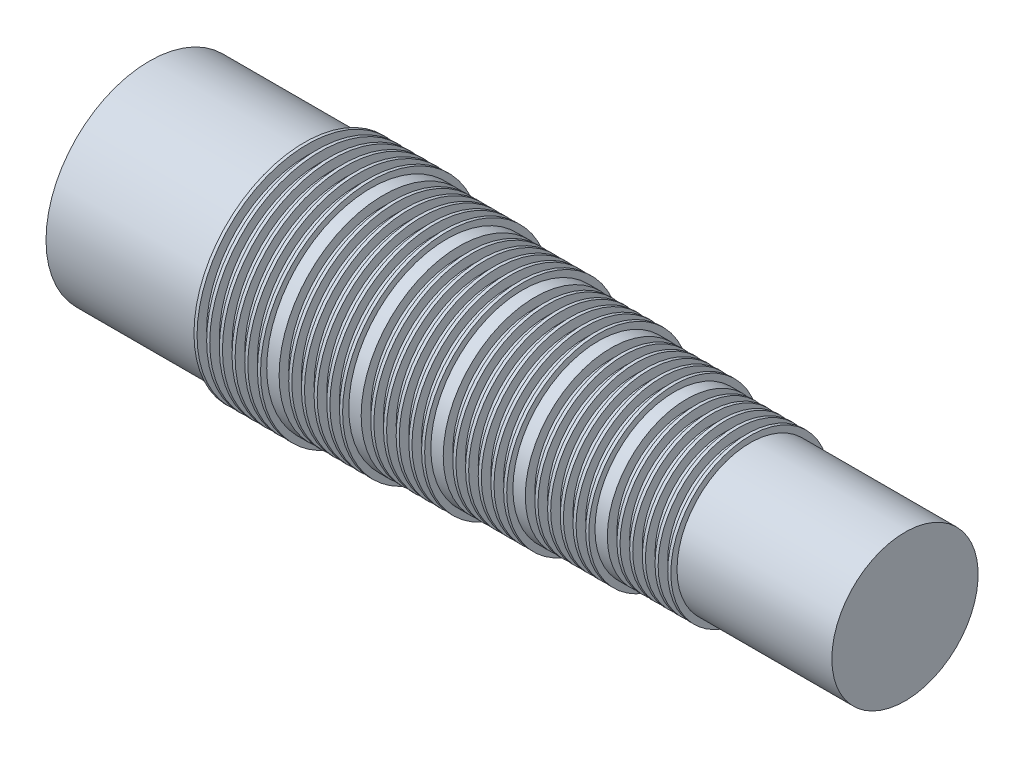
SolidWorks part; units mm, degrees
ref_plane "Front Plane" through (0, 0, 0) normal (0, 0, 1) x (1, 0, 0)
ref_plane "Top Plane" through (0, 0, 0) normal (0, 1, 0) x (1, 0, 0)
ref_plane "Right Plane" through (0, 0, 0) normal (1, 0, 0) x (0, 0, -1)
sketch "Sketch1" plane through (0, 0, 0) normal (0, 0, 1) x (1, 0, 0)
  line L24 (12.954, 9.048) -> (12.954, 8.2606)
  line L25 (12.954, 8.2606) -> (13.7414, 8.2606)
  line L26 (13.7414, 8.2606) -> (13.7414, 9.048)
  line L27 (13.7414, 9.048) -> (13.9954, 9.048)
  line L28 (13.9954, 9.048) -> (13.9954, 8.2606)
  line L29 (13.9954, 8.2606) -> (14.7828, 8.2606)
  line L30 (14.7828, 8.2606) -> (14.7828, 9.048)
  line L31 (14.7828, 9.048) -> (15.0368, 9.048)
  line L32 (15.0368, 9.048) -> (15.0368, 8.2606)
  line L33 (15.0368, 8.2606) -> (15.8242, 8.2606)
  line L34 (15.8242, 8.2606) -> (15.8242, 9.048)
  line L35 (15.8242, 9.048) -> (16.0782, 9.048)
  line L36 (16.0782, 9.048) -> (16.0782, 8.2606)
  line L37 (16.0782, 8.2606) -> (16.8656, 8.2606)
  line L38 (16.8656, 8.2606) -> (16.8656, 9.048)
  line L39 (16.8656, 9.048) -> (17.1196, 9.048)
  line L40 (17.1196, 9.048) -> (17.1196, 8.2606)
  line L41 (17.1196, 8.2606) -> (17.907, 8.2606)
  line L42 (17.907, 8.2606) -> (17.907, 9.048)
  line L43 (17.907, 9.048) -> (18.161, 9.048)
  line L44 (18.161, 9.048) -> (18.161, 8.54)
  line L45 (18.161, 8.54) -> (19.177, 8.54)
  line L46 (19.177, 8.54) -> (19.177, 7.7526)
  line L47 (19.177, 7.7526) -> (19.9644, 7.7526)
  line L48 (19.9644, 7.7526) -> (19.9644, 8.54)
  line L49 (19.9644, 8.54) -> (20.2184, 8.54)
  line L50 (20.2184, 8.54) -> (20.2184, 7.7526)
  line L51 (20.2184, 7.7526) -> (21.0058, 7.7526)
  line L52 (21.0058, 7.7526) -> (21.0058, 8.54)
  line L53 (21.0058, 8.54) -> (21.2598, 8.54)
  line L54 (21.2598, 8.54) -> (21.2598, 7.7526)
  line L55 (21.2598, 7.7526) -> (22.0472, 7.7526)
  line L56 (22.0472, 7.7526) -> (22.0472, 8.54)
  line L57 (22.0472, 8.54) -> (22.3012, 8.54)
  line L58 (22.3012, 8.54) -> (22.3012, 7.7526)
  line L59 (22.3012, 7.7526) -> (23.0886, 7.7526)
  line L60 (23.0886, 7.7526) -> (23.0886, 8.54)
  line L61 (23.0886, 8.54) -> (23.3426, 8.54)
  line L62 (23.3426, 8.54) -> (23.3426, 7.7526)
  line L63 (23.3426, 7.7526) -> (24.13, 7.7526)
  line L64 (24.13, 7.7526) -> (24.13, 8.54)
  line L65 (24.13, 8.54) -> (24.384, 8.54)
  line L66 (24.384, 8.54) -> (24.384, 8.032)
  line L67 (24.384, 8.032) -> (25.4, 8.032)
  line L68 (25.4, 8.032) -> (25.4, 7.2446)
  line L69 (25.4, 7.2446) -> (26.1874, 7.2446)
  line L70 (26.1874, 7.2446) -> (26.1874, 8.032)
  line L71 (26.1874, 8.032) -> (26.4414, 8.032)
  line L72 (26.4414, 8.032) -> (26.4414, 7.2446)
  line L73 (26.4414, 7.2446) -> (27.2288, 7.2446)
  line L74 (27.2288, 7.2446) -> (27.2288, 8.032)
  line L75 (27.2288, 8.032) -> (27.4828, 8.032)
  line L76 (27.4828, 8.032) -> (27.4828, 7.2446)
  line L77 (27.4828, 7.2446) -> (28.2702, 7.2446)
  line L78 (28.2702, 7.2446) -> (28.2702, 8.032)
  line L79 (28.2702, 8.032) -> (28.5242, 8.032)
  line L80 (28.5242, 8.032) -> (28.5242, 7.2446)
  line L81 (28.5242, 7.2446) -> (29.3116, 7.2446)
  line L82 (29.3116, 7.2446) -> (29.3116, 8.032)
  line L83 (29.3116, 8.032) -> (29.5656, 8.032)
  line L84 (29.5656, 8.032) -> (29.5656, 7.2446)
  line L85 (29.5656, 7.2446) -> (30.353, 7.2446)
  line L86 (30.353, 7.2446) -> (30.353, 8.032)
  line L87 (30.353, 8.032) -> (30.607, 8.032)
  line L88 (30.607, 8.032) -> (30.607, 7.524)
  line L89 (30.607, 7.524) -> (31.623, 7.524)
  line L90 (31.623, 7.524) -> (31.623, 6.7366)
  line L91 (31.623, 6.7366) -> (32.4104, 6.7366)
  line L92 (32.4104, 6.7366) -> (32.4104, 7.524)
  line L93 (32.4104, 7.524) -> (32.6644, 7.524)
  line L94 (32.6644, 7.524) -> (32.6644, 6.7366)
  line L95 (32.6644, 6.7366) -> (33.4518, 6.7366)
  line L96 (33.4518, 6.7366) -> (33.4518, 7.524)
  line L97 (33.4518, 7.524) -> (33.7058, 7.524)
  line L98 (33.7058, 7.524) -> (33.7058, 6.7366)
  line L99 (33.7058, 6.7366) -> (34.4932, 6.7366)
  line L100 (34.4932, 6.7366) -> (34.4932, 7.524)
  line L101 (34.4932, 7.524) -> (34.7472, 7.524)
  line L102 (34.7472, 7.524) -> (34.7472, 6.7366)
  line L103 (34.7472, 6.7366) -> (35.5346, 6.7366)
  line L104 (35.5346, 6.7366) -> (35.5346, 7.524)
  line L105 (35.5346, 7.524) -> (35.7886, 7.524)
  line L106 (35.7886, 7.524) -> (35.7886, 6.7366)
  line L107 (35.7886, 6.7366) -> (36.576, 6.7366)
  line L108 (36.576, 6.7366) -> (36.576, 7.524)
  line L109 (36.576, 7.524) -> (36.83, 7.524)
  line L110 (36.83, 7.524) -> (36.83, 7.016)
  line L111 (36.83, 7.016) -> (37.846, 7.016)
  line L112 (37.846, 7.016) -> (37.846, 6.2286)
  line L113 (37.846, 6.2286) -> (38.6334, 6.2286)
  line L114 (38.6334, 6.2286) -> (38.6334, 7.016)
  line L115 (38.6334, 7.016) -> (38.8874, 7.016)
  line L116 (38.8874, 7.016) -> (38.8874, 6.2286)
  line L117 (38.8874, 6.2286) -> (39.6748, 6.2286)
  line L118 (39.6748, 6.2286) -> (39.6748, 7.016)
  line L119 (39.6748, 7.016) -> (39.9288, 7.016)
  line L120 (39.9288, 7.016) -> (39.9288, 6.2286)
  line L121 (39.9288, 6.2286) -> (40.7162, 6.2286)
  line L122 (40.7162, 6.2286) -> (40.7162, 7.016)
  line L123 (40.7162, 7.016) -> (40.9702, 7.016)
  line L124 (40.9702, 7.016) -> (40.9702, 6.2286)
  line L125 (40.9702, 6.2286) -> (41.7576, 6.2286)
  line L126 (41.7576, 6.2286) -> (41.7576, 7.016)
  line L127 (41.7576, 7.016) -> (42.0116, 7.016)
  line L128 (42.0116, 7.016) -> (42.0116, 6.2286)
  line L129 (42.0116, 6.2286) -> (42.799, 6.2286)
  line L130 (42.799, 6.2286) -> (42.799, 7.016)
  line L131 (42.799, 7.016) -> (43.053, 7.016)
  line L132 (43.053, 7.016) -> (43.053, 6.508)
  line L133 (43.053, 6.508) -> (44.069, 6.508)
  line L134 (44.069, 6.508) -> (44.069, 5.7206)
  line L135 (44.069, 5.7206) -> (44.8564, 5.7206)
  line L136 (44.8564, 5.7206) -> (44.8564, 6.508)
  line L137 (44.8564, 6.508) -> (45.1104, 6.508)
  line L138 (45.1104, 6.508) -> (45.1104, 5.7206)
  line L139 (45.1104, 5.7206) -> (45.8978, 5.7206)
  line L140 (45.8978, 5.7206) -> (45.8978, 6.508)
  line L141 (45.8978, 6.508) -> (46.1518, 6.508)
  line L142 (46.1518, 6.508) -> (46.1518, 5.7206)
  line L143 (46.1518, 5.7206) -> (46.9392, 5.7206)
  line L144 (46.9392, 5.7206) -> (46.9392, 6.508)
  line L145 (46.9392, 6.508) -> (47.1932, 6.508)
  line L146 (47.1932, 6.508) -> (47.1932, 5.7206)
  line L147 (47.1932, 5.7206) -> (47.9806, 5.7206)
  line L148 (47.9806, 5.7206) -> (47.9806, 6.508)
  line L149 (47.9806, 6.508) -> (48.2346, 6.508)
  line L150 (48.2346, 6.508) -> (48.2346, 5.7206)
  line L151 (48.2346, 5.7206) -> (49.022, 5.7206)
  line L152 (49.022, 5.7206) -> (49.022, 6.508)
  line L153 (49.022, 6.508) -> (49.276, 6.508)
  line L154 (49.276, 6.508) -> (49.276, 6)
  line L155 (49.276, 6) -> (61.976, 6)
  line L156 (12.7, 8.4836) -> (0, 8.4836)
  line L157 (0, 8.4836) -> (0, 0)
  line L158 (0, 0) -> (61.976, 0)
  line L159 (61.976, 0) -> (61.976, 6)
  line L160 (12.954, 9.048) -> (12.7, 9.048)
  line L161 (12.7, 9.048) -> (12.7, 8.4836)
  point P1 (0, 0)
  dimension "D1" = 8.4836
  dimension "D2" = 6
  dimension "D8" = 12.7
  dimension "D9" = 12.7
  dimension "D3" = 0.254
  dimension "D4" = 0.7874
  dimension "D5" = 0.7874
  dimension "D6" = 0.508
  dimension "D7" = 1.016
revolve "Revolve1" add sketch "Sketch1" angle 360 about L158
equation "\"kero_radius\"=0.334in"
equation "\"D1@Sketch1\"=\"kero_radius\""
equation "\"lox_radius\"=0.23622in"
equation "\"D2@Sketch1\"=\"lox_radius\""
equation "\"Cavity_width\"=0.031in"
equation "\"tooth_width\"=0.01in"
equation "\"cavity_depth\"=0.031in"
equation "\"seal_step\"=0.02in"
equation "\"purge_length\"=0.04in"
equation "\"D3@Sketch1\"=\"tooth_width\""
equation "\"D4@Sketch1\"=\"Cavity_width\""
equation "\"D5@Sketch1\"=\"cavity_depth\""
equation "\"D6@Sketch1\"=\"seal_step\""
equation "\"D7@Sketch1\"=\"purge_length\""
